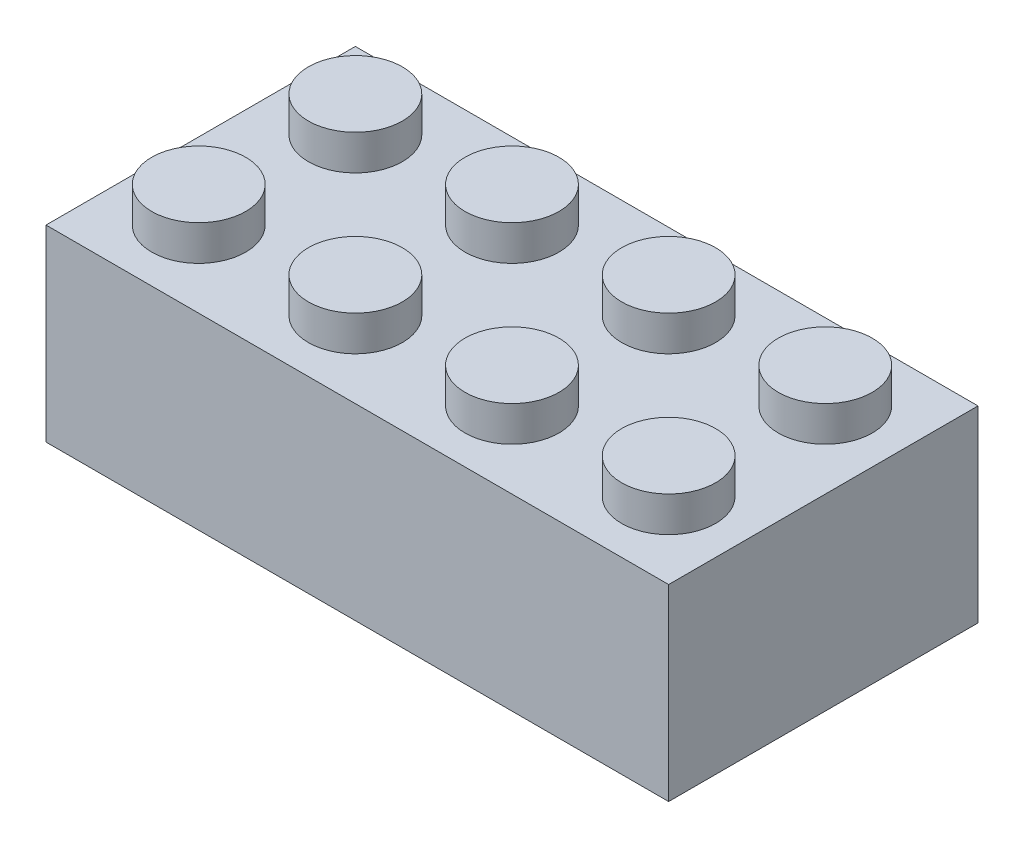
SolidWorks part; units mm, degrees
ref_plane "Front Plane" through (0, 0, 0) normal (0, 0, 1) x (1, 0, 0)
ref_plane "Top Plane" through (0, 0, 0) normal (0, 1, 0) x (1, 0, 0)
ref_plane "Right Plane" through (0, 0, 0) normal (1, 0, 0) x (0, 0, -1)
sketch "Sketch1" plane through (0, 0, 0) normal (0, 1, 0) x (1, 0, 0)
  line L1 (15.9, -7.9) -> (-15.9, -7.9)
  line L2 (15.9, -7.9) -> (15.9, 7.9)
  line L3 (15.9, 7.9) -> (-15.9, 7.9)
  line L4 (-15.9, -7.9) -> (-15.9, 7.9)
  line L5 (15.9, -7.9) -> (-15.9, 7.9) construction
  line L6 (15.9, 7.9) -> (-15.9, -7.9) construction
  point P0 (0, 0)
  dimension "D1" = 15.8
  dimension "D2" = 31.8
extrude "Boss-Extrude1" add sketch "Sketch1" along normal blind 9.6
sketch "Sketch2" plane through (0, 9.6, 0) normal (0, 1, 0) x (1, 0, 0)
  line L1 (0, 0) -> (0, 10.3714) construction
  circle A0 centre (-12, 4) radius 2.4
  dimension "D1" = 4.8
  dimension "D2" = 12
  dimension "D3" = 4
extrude "Boss-Extrude2" add sketch "Sketch2" along normal blind 1.8
sketch "Sketch4" plane through (0, 0, 0) normal (0, 1, 0) x (1, 0, 0)
  line L4 (-12.6, 6.7) -> (-12.6, 6.5)
  line L5 (-12.6, 6.5) -> (-11.4, 6.5)
  line L6 (-11.4, 6.5) -> (-11.4, 6.7)
  line L7 (-12.6, 6.7) -> (-14.7, 6.7)
  line L8 (-14.7, 6.7) -> (-14.7, -6.7)
  line L9 (-14.7, -6.7) -> (14.7, -6.7)
  line L10 (14.7, -6.7) -> (14.7, 6.7)
  line L11 (14.7, 6.7) -> (-14.7, 6.7)
  line L12 (-14.7, 6.7) -> (-14.7, 4.6)
  line L13 (-14.7, -6.7) -> (-12.6, -6.7)
  line L14 (14.7, -6.7) -> (14.7, -4.6)
  line L15 (14.7, 6.7) -> (-11.4, 6.7)
  line L16 (-14.7, 4.6) -> (-14.5, 4.6)
  line L17 (-14.5, 4.6) -> (-14.5, 3.4)
  line L18 (-14.5, 3.4) -> (-14.7, 3.4)
  line L19 (-14.7, 3.4) -> (-14.7, -3.4)
  line L20 (0, 0) -> (-26.2659, 0) construction
  line L21 (-14.5, -3.4) -> (-14.7, -3.4)
  line L22 (-14.5, -4.6) -> (-14.5, -3.4)
  line L23 (-14.7, -4.6) -> (-14.5, -4.6)
  line L24 (-11.4, -6.5) -> (-11.4, -6.7)
  line L25 (-12.6, -6.5) -> (-11.4, -6.5)
  line L26 (-12.6, -6.7) -> (-12.6, -6.5)
  line L27 (-14.7, -4.6) -> (-14.7, -6.7)
  line L28 (-11.4, -6.7) -> (14.7, -6.7)
  line L29 (0, 0) -> (0, 14.6051) construction
  line L30 (14.7, -4.6) -> (14.5, -4.6)
  line L31 (14.5, -4.6) -> (14.5, -3.4)
  line L32 (14.5, -3.4) -> (14.7, -3.4)
  line L33 (14.5, 3.4) -> (14.7, 3.4)
  line L34 (14.5, 4.6) -> (14.5, 3.4)
  line L35 (14.7, 4.6) -> (14.5, 4.6)
  line L36 (14.7, 4.6) -> (14.7, 6.7)
  line L37 (14.7, -3.4) -> (14.7, 3.4)
  circle A0 centre (-8, 0) radius 3.25
  circle A1 centre (-8, 0) radius 2.05
  circle A2 centre (0, 0) radius 3.25
  circle A3 centre (0, 0) radius 2.05
  circle A4 centre (8, 0) radius 3.25
  circle A5 centre (8, 0) radius 2.05
  point P7 (-12, 6.5)
  point P15 (-14.5, 4)
  dimension "D4" = 6.5
  dimension "D6" = 1.2
  dimension "D2" = 0.2
  dimension "D3" = 1.2
  dimension "D5" = 8
  dimension "D7" = 4
  dimension "D8" = 4
  dimension "D1" = 1.2
  dimension "D9" = 3
extrude "Cut-Extrude1" cut sketch "Sketch4" along normal offset from surface (8.6 mm away) 1 contours L37 L32 L31 L30 L14 L28 L24 L25 L26 L13 L27 L23 L22 L21 L19 L18 L17 L16 L12 L7 L4 L5 L6 L15 L36 L35 L34 L33 A2 A0 A4 | A1 | A3 | A5 region at (-12.9231, 0, -6.6) region at (-8, 0, 0) region at (0, 0, 0) region at (8, 0, 0) up to face at (-12, 9.6, -1.6)
pattern_linear "LPattern1" count 4 spacing 8 along (1, 0, 0) of face at (-12, 4.3, -6.5) of face at (-11.4, 4.3, -6.6) of face at (-12.6, 4.3, -6.6) of face at (-12.6, 4.3, 6.6) of face at (-12, 4.3, 6.5) of face at (-11.4, 4.3, 6.6)
sketch "Sketch5" plane through (0, 8.6, 0) normal (0, -1, 0) x (1, 0, 0)
  circle A3 centre (-12, -4) radius 1.3
  point P0 (-12, -4)
  dimension "D1" = 2.6
extrude "Cut-Extrude2" cut sketch "Sketch5" against normal offset from surface (1.7 mm away) 1.1 up to face at (-12, 11.4, -1.6)
pattern_linear "LPattern9" count 4 spacing 8 along (1, 0, 0) count 2 spacing 8 along (0, 0, 1) of "Boss-Extrude2", "Cut-Extrude2"
sketch "Sketch6" plane through (0, 8.6, 0) normal (0, -1, 0) x (1, 0, 0)
  line L0 (-0.55, 6.7) -> (-0.55, 3.2031)
  line L1 (-3.4, 6.7) -> (3.4, 6.7) construction
  line L2 (0.55, 6.7) -> (0.55, 3.2031)
  line L3 (-3.4, 6.7) -> (3.4, 6.7) construction
  line L4 (0, 3.25) -> (0, 10.6825) construction
  line L5 (-0.55, 6.7) -> (0.55, 6.7)
  line L6 (0, 0) -> (14.7, 0) construction
  line L7 (14.7, 3.4) -> (14.7, -3.4) construction
  line L8 (0.55, -6.7) -> (0.55, -3.2031)
  line L9 (-0.55, -6.7) -> (0.55, -6.7)
  line L10 (-0.55, -6.7) -> (-0.55, -3.2031)
  line L11 (3.4, -6.7) -> (-3.4, -6.7) construction
  circle A0 centre (0, 0) radius 3.25 construction
  circle A1 centre (0, 0) radius 3.25 construction
  arc A2 (0.55, 3.2031) -> (-0.55, 3.2031) centre (0, 0) ccw
  arc A3 (0.55, -3.2031) -> (-0.55, -3.2031) centre (0, 0) cw
  point P24 (1.084, -6.7)
  point P27 (0.5662, -6.7)
  dimension "D1" = 1.1
extrude "Boss-Extrude3" add sketch "Sketch6" along normal offset from surface (6.3 mm away) 2.3 up to face at (0, 0, 0)
